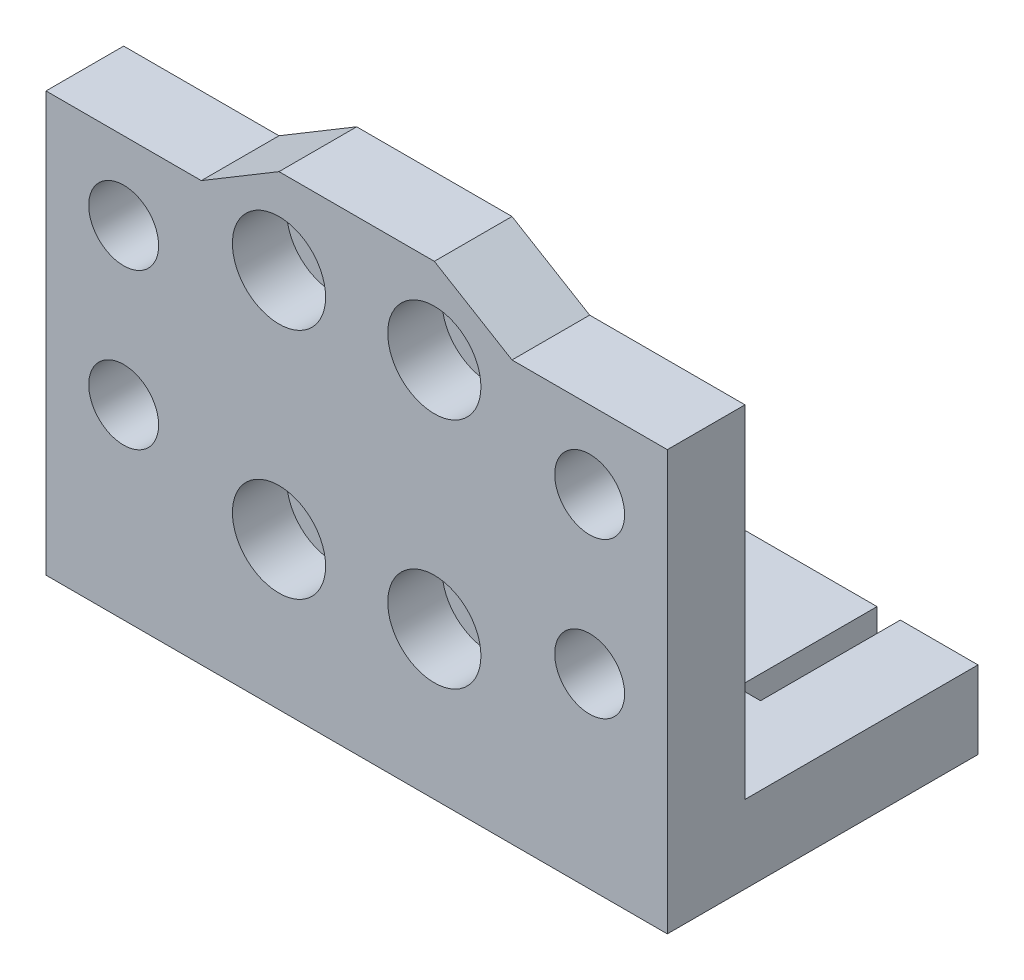
SolidWorks part; units mm, degrees
ref_plane "前视基准面" through (0, 0, 0) normal (0, 0, 1) x (1, 0, 0)
ref_plane "上视基准面" through (0, 0, 0) normal (0, 1, 0) x (1, 0, 0)
ref_plane "右视基准面" through (0, 0, 0) normal (1, 0, 0) x (0, 0, -1)
other "Configuration Table"
sketch "Sketch1" plane through (0, 0, 0) normal (0, 0, 1) x (1, 0, 0)
  line L1 (-20, -13.5) -> (20, -13.5)
  line L2 (-20, -13.5) -> (-20, 13.5)
  line L3 (-20, 13.5) -> (20, 13.5)
  line L4 (20, -13.5) -> (20, 13.5)
  line L5 (-20, -13.5) -> (20, 13.5) construction
  line L6 (-20, 13.5) -> (20, -13.5) construction
  point P0 (0, 0)
  dimension "D1" = 40
  dimension "D2" = 27
extrude "Boss-Extrude1" add sketch "Sketch1" along normal blind 5
sketch "Sketch2" plane through (0, 0, 0) normal (0, 0, -1) x (-1, 0, 0)
  line L0 (-20, -13.5) -> (-20, 13.5) construction
  line L1 (-20, -8.5) -> (20, -8.5)
  line L2 (-20, -8.5) -> (-20, -13.5)
  line L3 (-20, -13.5) -> (20, -13.5)
  line L4 (20, -8.5) -> (20, -13.5)
  line L5 (-20, 13.5) -> (20, 13.5) construction
  dimension "D1" = 22
extrude "Boss-Extrude2" add sketch "Sketch2" along normal blind 15
sketch "Sketch3" plane through (0, 0, 5) normal (0, 0, 1) x (1, 0, 0)
  line L0 (20, 13.5) -> (-20, 13.5) construction
  circle A0 centre (-5, 11) radius 1.65
  circle A1 centre (5, 11) radius 1.65
  circle A2 centre (5, -4) radius 1.65
  circle A3 centre (-5, -4) radius 1.65
  dimension "D1" = 3.3
  dimension "D2" = 2.5
  dimension "D3" = 5
  dimension "D4" = 2
  dimension "D5" = 2
extrude "Cut-Extrude1" cut sketch "Sketch3" against normal blind 15
sketch "Sketch4" plane through (0, 0, 5) normal (0, 0, 1) x (1, 0, 0)
  line L0 (-10, 13.5) -> (-5, 16.5)
  line L1 (20, 13.5) -> (-20, 13.5) construction
  line L2 (-5, 16.5) -> (5, 16.5)
  line L3 (5, 16.5) -> (10, 13.5)
  line L4 (10, 13.5) -> (-10, 13.5)
  circle A0 centre (-5, 11) radius 1.65 construction
  circle A1 centre (5, 11) radius 1.65 construction
  dimension "D1" = 5
  dimension "D2" = 5
  dimension "D3" = 5
  dimension "D4" = 5
  dimension "D5" = 3
extrude "Boss-Extrude3" add sketch "Sketch4" against normal blind 5
sketch "Sketch5" plane through (0, 0, 5) normal (0, 0, 1) x (1, 0, 0)
  circle A0 centre (-5, 11) radius 3
  circle A1 centre (5, 11) radius 3
  circle A2 centre (5, -4) radius 3
  circle A3 centre (-5, -4) radius 3
  dimension "D1" = 6
  dimension "D2" = 2
  dimension "D3" = 2
extrude "Cut-Extrude2" cut sketch "Sketch5" against normal blind 3.5
sketch "Sketch6" plane through (0, -8.5, 0) normal (0, 1, 0) x (1, 0, 0)
  line L0 (-20, 15) -> (20, 15) construction
  line L1 (-15, 15) -> (-13.5, 15)
  line L2 (-15, 15) -> (-15, 6)
  line L3 (-15, 6) -> (-13.5, 6)
  line L4 (-13.5, 15) -> (-13.5, 6)
  line L5 (-10, 0) -> (-20, 0) construction
  line L6 (13.5, 15) -> (15, 15)
  line L7 (13.5, 15) -> (13.5, 6)
  line L8 (13.5, 6) -> (15, 6)
  line L9 (15, 15) -> (15, 6)
  line L10 (-20, 15) -> (-20, 0) construction
  line L11 (20, 15) -> (20, 0) construction
  dimension "D1" = 6
  dimension "D2" = 1.5
  dimension "D3" = 1.5
  dimension "D4" = 5
  dimension "D5" = 5
extrude "Cut-Extrude3" cut sketch "Sketch6" against normal blind 5
sketch "Sketch7" plane through (0, 0, 5) normal (0, 0, 1) x (1, 0, 0)
  line L0 (-20, 13.5) -> (-20, -13.5) construction
  line L1 (-10, 13.5) -> (-20, 13.5) construction
  circle A0 centre (-15, 8.5) radius 2.25
  circle A1 centre (15, 8.5) radius 2.25
  circle A2 centre (15, -1.5) radius 2.25
  circle A3 centre (-15, -1.5) radius 2.25
  dimension "D1" = 4.5
  dimension "D2" = 5
  dimension "D3" = 5
  dimension "D4" = 2
  dimension "D5" = 2
extrude "Cut-Extrude4" cut sketch "Sketch7" against normal blind 5
